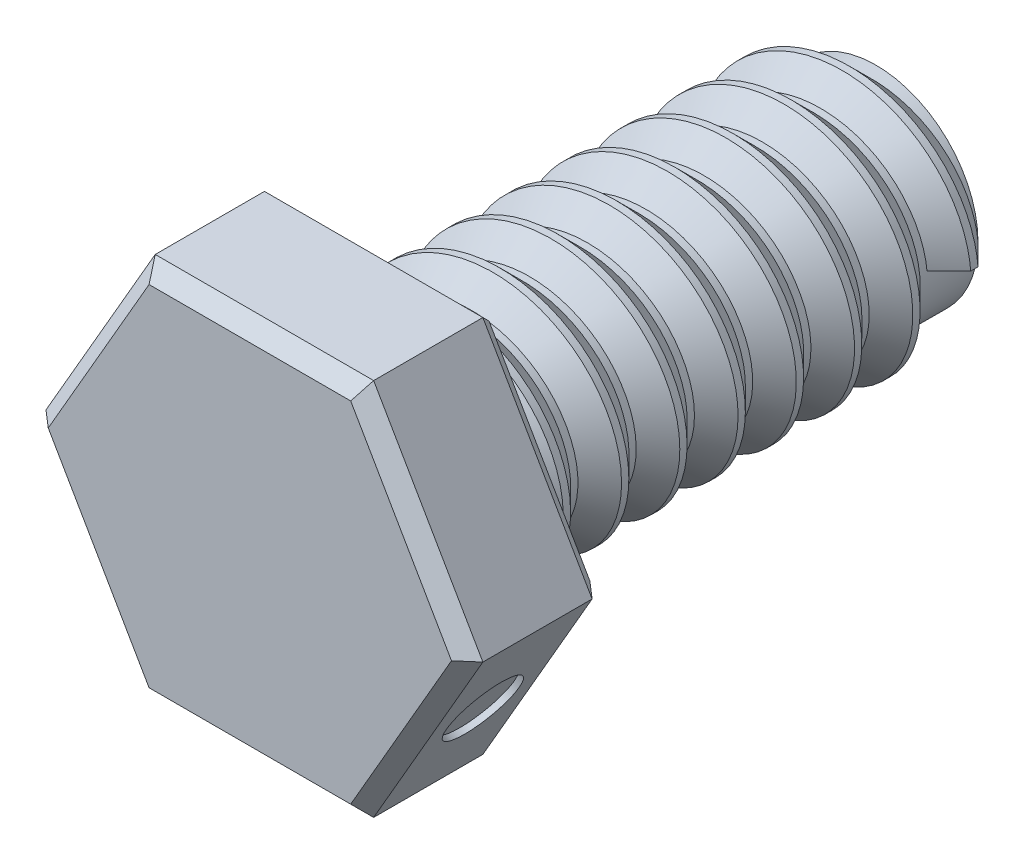
SolidWorks part; units mm, degrees
ref_plane "前视基准面" through (0, 0, 0) normal (0, 0, 1) x (1, 0, 0)
ref_plane "上视基准面" through (0, 0, 0) normal (0, 1, 0) x (1, 0, 0)
ref_plane "右视基准面" through (0, 0, 0) normal (1, 0, 0) x (0, 0, -1)
sketch "草图1" plane through (0, 0, 0) normal (0, 0, 1) x (1, 0, 0)
  line L1 (15, 0) -> (7.5, 12.9904)
  line L2 (7.5, 12.9904) -> (-7.5, 12.9904)
  line L3 (-7.5, 12.9904) -> (-15, 0)
  line L4 (-15, 0) -> (-7.5, -12.9904)
  line L5 (-7.5, -12.9904) -> (7.5, -12.9904)
  line L6 (7.5, -12.9904) -> (15, 0)
  circle A0 centre (0, 0) radius 15
  circle A1 centre (0, 0) radius 12.9904 construction
  dimension "D1" = 30
extrude "凸台-拉伸1" add sketch "草图1" along normal blind 9.5 contours L2 L3 L4 L5 L6 L1
sketch "草图2" plane through (0, 0, 0) normal (0, 0, -1) x (-1, 0, 0)
  circle A0 centre (0, 0) radius 7
  circle A1 centre (0, 0) radius 9
  dimension "D1" = 14
  dimension "D2" = 2
sketch "草图6" plane through (0, 0, 0) normal (0, 0, -1) x (-1, 0, 0)
  circle A0 centre (0, 0) radius 7 construction
  circle A1 centre (0, 0) radius 7
extrude "凸台-拉伸2" add sketch "草图6" along normal blind 33.5
sketch "草图5" plane through (0, 0, 0) normal (0, 0, -1) x (-1, 0, 0)
  circle A0 centre (0, 0) radius 7 construction
  circle A1 centre (0, 0) radius 7
ref_plane "基准面1" through (0, 0, -1.75) normal (0, 0, -1) x (-1, 0, 0)
sketch "草图7" plane through (0, 0, -1.75) normal (0, 0, -1) x (-1, 0, 0)
  circle A0 centre (0, 0) radius 7 construction
  circle A1 centre (0, 0) radius 7
curve "螺旋线/涡状线2" pitch 4 height 30 radius 7 centre (0, 0, -1.75) axis (0, 0, -1) start towards (-1, 0, 0)
sketch "草图8" plane through (0, 0, 0) normal (0, 1, 0) x (1, 0, 0)
  line L0 (-7, 3.5) -> (-7, 0)
  line L1 (-7, 0) -> (-8.5, 1.5)
  line L2 (-8.5, 1.5) -> (-8.5, 2)
  line L3 (-8.5, 2) -> (-7, 3.5)
  point P7 (-7, 1.75)
  dimension "D1" = 1.5
  dimension "D2" = 3.5
  dimension "D3" = 45
  dimension "D4" = 45
sweep "扫描1" add profiles "草图8" path "螺旋线/涡状线2"
sketch "草图9" plane through (0, 0, 0) normal (0, 1, 0) x (1, 0, 0)
  line L0 (9, 0) -> (-9, 0) construction
  line L1 (0, 0) -> (0, 50000) construction
  line L2 (7, 0) -> (7, 2) construction
  line L3 (7, 3.5) -> (7, 0)
  line L4 (7, 3.5) -> (8.5, 2)
  line L5 (8.5, 2) -> (8.5, 1.5)
  line L6 (8.5, 1.5) -> (7, 0)
  point P8 (11.4749, 6.2988)
  dimension "D1" = 3.5
  dimension "D2" = 45
  dimension "D3" = 45
  dimension "D4" = 1.5
revolve "旋转2" add sketch "草图9" angle 45 about L1 reverse direction yes
chamfer "倒角1" distance 1 angle 45 12 edges at (0, -12.9904, 0) (11.25, -6.4952, 0) (-11.25, -6.4952, 0) (-11.25, 6.4952, 0) (0, 12.9904, 0) (11.25, 6.4952, 0) (-11.25, 6.4952, 9.5) (-11.25, -6.4952, 9.5) (0, -12.9904, 9.5) (11.25, -6.4952, 9.5) (11.25, 6.4952, 9.5) (0, 12.9904, 9.5)
sketch "草图11" plane through (-11.25, -6.4952, 0) normal (-0.866, -0.5, 0) x (0, 0, 1)
  line L0 (1, 0) -> (8.5, 0) construction
  line L8 (1, 7.5) -> (1, -7.5) construction
  line L9 (8.5, -7.5) -> (8.5, 7.5) construction
  line L10 (2.25, 0) -> (7.25, 2.8868)
  line L11 (7.25, 2.8868) -> (7.25, -2.8868)
  line L12 (7.25, -2.8868) -> (2.25, 0)
  line L13 (2.25, 0) -> (7.25, 0) construction
  line L14 (4.75, 0) -> (4.75, -1.2379) construction
  point P12 (4.75, 0)
  dimension "D1" = 5
extrude "切除-拉伸2" cut sketch "草图11" against normal blind 0.4
sketch "草图12" plane through (0, -12.9904, 0) normal (0, -1, 0) x (1, 0, 0)
  line L0 (0, 8.5) -> (0, 1) construction
  line L1 (7.5, 8.5) -> (-7.5, 8.5) construction
  line L2 (-7.5, 1) -> (7.5, 1) construction
  line L3 (-2.5, 7.25) -> (2.5, 2.25) construction
  line L4 (2.5, 2.25) -> (-2.5, 2.25)
  line L5 (2.5, 2.25) -> (2.5, 7.25)
  line L6 (2.5, 7.25) -> (-2.5, 7.25)
  line L7 (-2.5, 2.25) -> (-2.5, 7.25)
  line L8 (0, 7.25) -> (0, 2.25) construction
  line L9 (2.5, 4.75) -> (-2.5, 4.75) construction
  line L10 (2.5, 7.25) -> (-2.5, 2.25) construction
  line L11 (-2.5, 6.8257) -> (2.0757, 2.25)
  line L12 (-2.0757, 7.25) -> (2.5, 2.6743)
  line L13 (2.0757, 7.25) -> (-2.5, 2.6743)
  line L14 (2.5, 6.8257) -> (-2.0757, 2.25)
  line L15 (-2.7121, 7.0379) -> (2.2879, 2.0379) construction
  line L16 (-2.2879, 7.4621) -> (2.7121, 2.4621) construction
  line L17 (2.2879, 7.4621) -> (-2.7121, 2.4621) construction
  line L18 (2.7121, 7.0379) -> (-2.2879, 2.0379) construction
  line L19 (-2.5, 6.8257) -> (-2.0757, 7.25)
  line L20 (2.0757, 7.25) -> (2.5, 6.8257)
  line L21 (-2.5, 2.6743) -> (-2.0757, 2.25)
  line L22 (2.0757, 2.25) -> (2.5, 2.6743)
  point P6 (0, 4.75)
  dimension "D1" = 5
  dimension "D2" = 0.3
  dimension "D3" = 0.3
  dimension "D4" = 0.3
  dimension "D5" = 0.3
sketch "草图13" plane through (11.25, -6.4952, 0) normal (0.866, -0.5, 0) x (0, 0, -1)
  line L0 (-8.5, 0) -> (-1, 0) construction
  line L1 (-8.5, 7.5) -> (-8.5, -7.5) construction
  line L2 (-1, -7.5) -> (-1, 7.5) construction
  circle A0 centre (-4.75, 0) radius 2.5
  dimension "D1" = 5
sketch "草图14" plane through (-11.25, 6.4952, 0) normal (-0.866, 0.5, 0) x (0, 0, 1)
  line L0 (1, 0) -> (8.5, 0) construction
  line L1 (1, 7.5) -> (1, -7.5) construction
  line L2 (8.5, -7.5) -> (8.5, 7.5) construction
  line L4 (7.25, -2.5) -> (2.25, -2.5)
  line L5 (7.25, -2.5) -> (7.25, 2.5)
  line L6 (7.25, 2.5) -> (2.25, 2.5)
  line L7 (2.25, -2.5) -> (2.25, 2.5)
  line L8 (4.75, 2.5) -> (4.75, -2.5) construction
  line L9 (7.25, 0) -> (2.25, 0) construction
  point P6 (4.75, 0)
  dimension "D1" = 5
extrude "切除-拉伸3" cut sketch "草图13" against normal blind 0.4 contours A0
extrude "切除-拉伸4" cut sketch "草图12" against normal blind 0.4 contours L13 L21 L14 L11 | L20 L13 L12 L14 | L11 L22 L12 L19 region at (-1.25, -12.9904, 3.5) region at (1.25, -12.9904, 6)
extrude "切除-拉伸5" cut sketch "草图14" against normal blind 0.4 contours L6 L7 L4 L5
